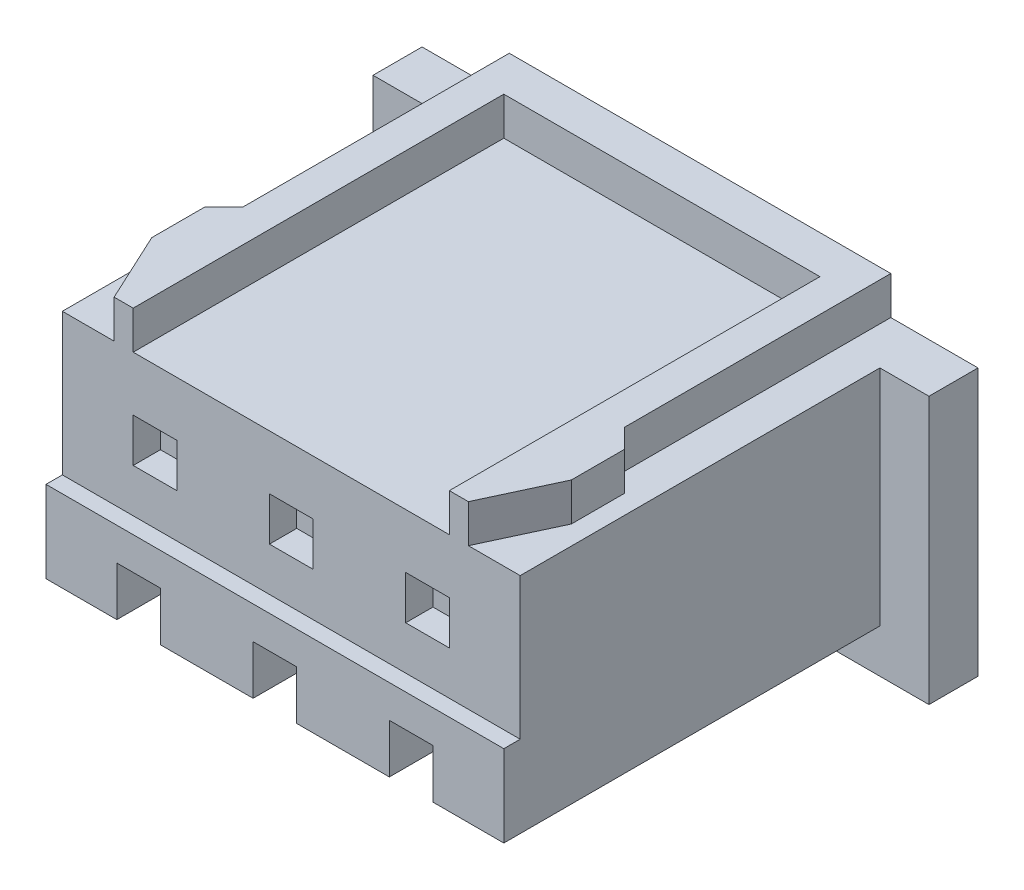
SolidWorks part; units mm, degrees
ref_plane "Plan de face" through (0, 0, 0) normal (0, 0, 1) x (1, 0, 0)
ref_plane "Plan de dessus" through (0, 0, 0) normal (0, 1, 0) x (1, 0, 0)
ref_plane "Plan de droite" through (0, 0, 0) normal (1, 0, 0) x (0, 0, -1)
sketch "Esquisse1" plane through (0, 0, 0) normal (0, 0, 1) x (1, 0, 0)
  line L1 (-5.1, 2.8) -> (5.1, 2.8)
  line L2 (-5.1, 2.8) -> (-5.1, -2.8)
  line L3 (-5.1, -2.8) -> (5.1, -2.8)
  line L4 (5.1, 2.8) -> (5.1, -2.8)
  line L5 (-5.1, 2.8) -> (5.1, -2.8) construction
  line L6 (-5.1, -2.8) -> (5.1, 2.8) construction
  point P0 (0, 0)
  dimension "D1" = 10.2
  dimension "D2" = 5.6
extrude "Boss.-Extru.1" add sketch "Esquisse1" against normal blind 7.8
sketch "Esquisse2" plane through (0, 0, 0) normal (0, 0, 1) x (1, 0, 0)
  line L0 (5.1, -2.8) -> (5.1, 2.8) construction
  line L1 (-5.1, 2.8) -> (5.1, 2.8)
  line L2 (-5.1, 2.8) -> (-5.1, -0.5)
  line L3 (-5.1, -0.5) -> (5.1, -0.5)
  line L4 (5.1, 2.8) -> (5.1, -0.5)
  dimension "D1" = 3.3
extrude "Enlèv. mat.-Extru.1" cut sketch "Esquisse2" against normal blind 0.3
sketch "Esquisse4" plane through (0, 0, 0) normal (0, 0, 1) x (1, 0, 0)
  line L0 (5.1, 2.8) -> (-5.1, 2.8) construction
  line L1 (-5.1, -2.8) -> (5.1, -2.8) construction
  line L2 (5.1, 2.8) -> (-5.1, 2.8)
  line L3 (-5.1, -2.8) -> (5.1, -2.8)
  line L4 (-4.2, 2.8) -> (-4.2, -2)
  line L5 (-4.2, -2) -> (4.2, -2)
  line L6 (4.2, -2) -> (4.2, 2.8)
  line L7 (-5.1, 2.8) -> (-5.1, -0.5) construction
  line L8 (5.1, -0.5) -> (5.1, 2.8) construction
  line L9 (-5.1, -0.5) -> (-5.1, -2.8) construction
  line L10 (5.1, -2.8) -> (5.1, -0.5) construction
  line L11 (-5.1, 2.8) -> (-5.1, -0.5)
  line L12 (-5.1, -0.5) -> (-5.1, -2.8)
  line L13 (5.1, -2.8) -> (5.1, -0.5)
  line L14 (5.1, -0.5) -> (5.1, 2.8)
  line M1 (5.1, -0.5) -> (-5.1, -0.5)
  line M2 (-5.1, -0.5) -> (-5.1, -2.8)
  line M3 (-5.1, -2.8) -> (5.1, -2.8)
  line M4 (5.1, -2.8) -> (5.1, -0.5)
  dimension "D1" = 0.9
  dimension "D2" = 0.9
  dimension "D3" = 0.8
extrude "Enlèv. mat.-Extru.2" cut sketch "Esquisse4" against normal blind 6.9 contours L2 L11 L4 M1 | L6 L5 L4 M1 M2 M3 M4 | L14 L2 L6 M1 region at (4.65, 1.15, 0) region at (0, -2.1141, 0) region at (-4.65, 1.15, 0)
sketch "Esquisse5" plane through (0, 2.8, 0) normal (0, 1, 0) x (1, 0, 0)
  line L0 (-3.5, 7.8) -> (-3.5, 2.91)
  line L1 (-3.5, 2.91) -> (-3.85, 2.56)
  line L2 (-3.85, 2.56) -> (-3.85, 1.59)
  line L3 (-3.85, 1.59) -> (-3.25, 0.3)
  line L4 (4.2, 0.3) -> (-4.2, 0.3) construction
  line L5 (-2.9, 0.3) -> (-2.9, 7.1)
  line L6 (-2.9, 7.1) -> (2.9, 7.1)
  line L7 (0, 7.8) -> (0, 0.3) construction
  line L8 (-5.1, 6.9) -> (-4.2, 6.9)
  line L9 (-4.2, 6.9) -> (-4.2, 0.3)
  line L10 (-4.2, 0.3) -> (4.2, 0.3)
  line L11 (4.2, 0.3) -> (4.2, 6.9)
  line L12 (4.2, 6.9) -> (5.1, 6.9)
  line L13 (5.1, 6.9) -> (5.1, 7.8)
  line L14 (5.1, 7.8) -> (-5.1, 7.8)
  line L15 (-5.1, 7.8) -> (-5.1, 6.9)
  line L16 (-5.1, 6.9) -> (-4.2, 6.9)
  line L17 (-4.2, 6.9) -> (-4.2, 0.3)
  line L18 (-4.2, 0.3) -> (4.2, 0.3)
  line L19 (4.2, 0.3) -> (4.2, 6.9)
  line L20 (4.2, 6.9) -> (5.1, 6.9)
  line L21 (5.1, 6.9) -> (5.1, 7.8)
  line L22 (5.1, 7.8) -> (-5.1, 7.8)
  line L23 (-5.1, 7.8) -> (-5.1, 6.9)
  line L24 (5.1, 7.8) -> (5.1, 6.9)
  line L25 (4.2, 6.9) -> (4.2, 0.3)
  line L26 (5.1, 6.9) -> (4.2, 6.9)
  line L27 (2.9, 0.3) -> (2.9, 7.1)
  line L28 (3.85, 1.59) -> (3.25, 0.3)
  line L29 (3.85, 2.56) -> (3.85, 1.59)
  line L30 (3.5, 2.91) -> (3.85, 2.56)
  line L31 (3.5, 7.8) -> (3.5, 2.91)
  point P21 (0, 7.1)
  line M9 (-5.1, 6.9) -> (-4.2, 6.9)
  line M10 (-4.2, 6.9) -> (-4.2, 0.3)
  line M11 (-4.2, 0.3) -> (4.2, 0.3)
  line M12 (4.2, 0.3) -> (4.2, 6.9)
  line M13 (4.2, 6.9) -> (5.1, 6.9)
  line M14 (5.1, 6.9) -> (5.1, 7.8)
  line M15 (5.1, 7.8) -> (-5.1, 7.8)
  line M16 (-5.1, 7.8) -> (-5.1, 6.9)
  dimension "D2" = 0.35
  dimension "D3" = 0.7
  dimension "D4" = 1.29
  dimension "D5" = 0.6
  dimension "D6" = 0.35
  dimension "D7" = 0.97
  dimension "D8" = 0.6
  dimension "D9" = 0.7
  dimension "D1" = 0
extrude "Enlèv. mat.-Extru.3" cut sketch "Esquisse5" against normal blind 0.7 contours L7 L6 L5 M11 | L6 L7 L18 L27 | L31 L30 L29 L28 M15 M11 M12 M13 M14 | L3 L2 L1 L0 M15 M16 M9 M10 M11 region at (-3.9793, 2.8, -4.6836) region at (-1.45, 2.8, -3.7) region at (1.45, 2.8, -3.7) region at (3.9793, 2.8, -4.6836)
sketch "Esquisse6" plane through (0, 0, 0) normal (0, 0, 1) x (1, 0, 0)
  line L0 (-2.9, -2) -> (-2.9, -1.1)
  line L1 (-4.2, -2) -> (4.2, -2) construction
  line L2 (-2.9, -1.1) -> (-2.1, -1.1)
  line L3 (-2.1, -1.1) -> (-2.1, -2)
  line L4 (-4.2, -0.5) -> (-4.2, -2) construction
  line L5 (-0.4, -2) -> (-0.4, -1.1)
  line L6 (-0.4, -1.1) -> (0.4, -1.1)
  line L7 (0.4, -1.1) -> (0.4, -2)
  line L9 (2.1, -2) -> (2.1, -1.1)
  line L10 (2.1, -1.1) -> (2.9, -1.1)
  line L11 (2.9, -1.1) -> (2.9, -2)
  line L13 (-2.9, -2) -> (-2.1, -2)
  line L14 (-0.4, -2) -> (0.4, -2)
  line L15 (2.1, -2) -> (2.9, -2)
  dimension "D1" = 1.3
  dimension "D2" = 0.9
  dimension "D3" = 0.8
  dimension "D4" = 1.7
  dimension "D5" = 1.7
  dimension "D6" = 0.8
  dimension "D7" = 0.8
extrude "Enlèv. mat.-Extru.4" cut sketch "Esquisse6" against normal blind 0.8
sketch "Esquisse7" plane through (0, 0, -0.3) normal (0, 0, 1) x (1, 0, 0)
  line L0 (-2.9, 2.1) -> (2.9, 2.1) construction
  line L1 (-2.9, 1.1) -> (-2.1, 1.1)
  line L2 (-2.9, 1.1) -> (-2.9, 0.3)
  line L3 (-2.9, 0.3) -> (-2.1, 0.3)
  line L4 (-2.1, 1.1) -> (-2.1, 0.3)
  line L5 (-0.4, 1.1) -> (0.4, 1.1)
  line L6 (-0.4, 1.1) -> (-0.4, 0.3)
  line L7 (-0.4, 0.3) -> (0.4, 0.3)
  line L8 (0.4, 1.1) -> (0.4, 0.3)
  line L9 (2.1, 1.1) -> (2.9, 1.1)
  line L10 (2.1, 1.1) -> (2.1, 0.3)
  line L11 (2.1, 0.3) -> (2.9, 0.3)
  line L12 (2.9, 1.1) -> (2.9, 0.3)
  line L13 (-2.9, -1.1) -> (-2.9, -2) construction
  line L14 (-0.4, -1.1) -> (-0.4, -2) construction
  line L15 (2.1, -1.1) -> (2.1, -2) construction
  dimension "D1" = 0.8
  dimension "D2" = 1
extrude "Enlèv. mat.-Extru.5" cut sketch "Esquisse7" against normal blind 0.5
sketch "Esquisse8" plane through (0, 0, -7.8) normal (0, 0, -1) x (-1, 0, 0)
  line L0 (-0.8, 1.5) -> (-0.8, -1.5)
  line L1 (-0.8, 1.5) -> (0.8, 1.5)
  line L2 (0, 1.5) -> (0, 0) construction
  line L3 (-3.5, 2.8) -> (3.5, 2.8) construction
  line L4 (-0.8, -1.5) -> (-0.4, -1.5)
  line L5 (-0.4, -1.5) -> (-0.4, -1.7)
  line L6 (-0.4, -1.7) -> (0.4, -1.7)
  line L7 (0.4, -1.7) -> (0.4, -1.5)
  line L8 (0.4, -1.5) -> (0.8, -1.5)
  line L9 (0.8, -1.5) -> (0.8, 1.5)
  line L10 (0, 0) -> (0, -1.7) construction
  line L11 (-0.7, 0.95) -> (-0.7, -1.45)
  line L12 (-0.7, -1.45) -> (0.7, -1.45)
  line L13 (0.7, -1.45) -> (0.7, 0.95)
  line L14 (0, -1.45) -> (0, 0.95) construction
  line L15 (1.7, 1.5) -> (1.7, -1.5)
  line L16 (1.7, 1.5) -> (3.3, 1.5)
  line L17 (1.7, -1.5) -> (2.1, -1.5)
  line L18 (2.1, -1.5) -> (2.1, -1.7)
  line L19 (2.1, -1.7) -> (2.9, -1.7)
  line L20 (2.9, -1.7) -> (2.9, -1.5)
  line L21 (2.9, -1.5) -> (3.3, -1.5)
  line L22 (3.3, -1.5) -> (3.3, 1.5)
  line L23 (1.8, 0.95) -> (1.8, -1.45)
  line L24 (1.8, -1.45) -> (3.2, -1.45)
  line L25 (3.2, -1.45) -> (3.2, 0.95)
  line L26 (2.5, 1.5) -> (2.5, 0) construction
  line L27 (2.5, 0) -> (2.5, -1.7) construction
  line L28 (2.5, -1.45) -> (2.5, 0.95) construction
  line L29 (-3.3, 1.5) -> (-3.3, -1.5)
  line L30 (-3.3, 1.5) -> (-1.7, 1.5)
  line L31 (-3.3, -1.5) -> (-2.9, -1.5)
  line L32 (-2.9, -1.5) -> (-2.9, -1.7)
  line L33 (-2.9, -1.7) -> (-2.1, -1.7)
  line L34 (-2.1, -1.7) -> (-2.1, -1.5)
  line L35 (-2.1, -1.5) -> (-1.7, -1.5)
  line L36 (-1.7, -1.5) -> (-1.7, 1.5)
  line L37 (-3.2, 0.95) -> (-3.2, -1.45)
  line L38 (-3.2, -1.45) -> (-1.8, -1.45)
  line L39 (-1.8, -1.45) -> (-1.8, 0.95)
  line L40 (-2.5, 1.5) -> (-2.5, 0) construction
  line L41 (-2.5, 0) -> (-2.5, -1.7) construction
  line L42 (-2.5, -1.45) -> (-2.5, 0.95) construction
  arc A0 (-0.7, 0.95) -> (0, 0.95) centre (-0.35, 0.95) cw
  arc A1 (0, 0.95) -> (0.7, 0.95) centre (0.35, 0.95) cw
  arc A2 (1.8, 0.95) -> (2.5, 0.95) centre (2.15, 0.95) cw
  arc A3 (2.5, 0.95) -> (3.2, 0.95) centre (2.85, 0.95) cw
  arc A4 (-3.2, 0.95) -> (-2.5, 0.95) centre (-2.85, 0.95) cw
  arc A5 (-2.5, 0.95) -> (-1.8, 0.95) centre (-2.15, 0.95) cw
  dimension "D1" = 3
  dimension "D2" = 1.6
  dimension "D3" = 1.3
  dimension "D4" = 0.8
  dimension "D5" = 0.2
  dimension "D6" = 0.05
  dimension "D7" = 0.1
  dimension "D8" = 0.1
  dimension "D9" = 2.4
  dimension "D11" = 2.5
  dimension "D13" = 2.5
  dimension "D10" = 2
  dimension "D12" = 2
extrude "Enlèv. mat.-Extru.6" cut sketch "Esquisse8" against normal blind 7 contours L8 L9 L1 L0 L4 L5 L6 L7 A0 A1 L13 L12 L11 | L35 L36 L30 L29 L31 L32 L33 L34 A4 A5 L39 L38 L37 | L21 L22 L16 L15 L17 L18 L19 L20 A2 A3 L25 L24 L23 region at (0, 1.4642, -7.8) region at (-2.5, 1.4642, -7.8) region at (2.5, 1.4642, -7.8)
sketch "Esquisse9" plane through (0, 0, -7.8) normal (0, 0, -1) x (-1, 0, 0)
  line L0 (-0.7, 0.95) -> (-0.7, -1.45) construction
  line L1 (-0.7, -1.45) -> (0.7, -1.45) construction
  line L2 (0.7, -1.45) -> (0.7, 0.95) construction
  line L3 (-3.2, 0.95) -> (-3.2, -1.45) construction
  line L4 (-3.2, -1.45) -> (-1.8, -1.45) construction
  line L5 (-1.8, -1.45) -> (-1.8, 0.95) construction
  line L6 (1.8, 0.95) -> (1.8, -1.45) construction
  line L7 (1.8, -1.45) -> (3.2, -1.45) construction
  line L8 (3.2, -1.45) -> (3.2, 0.95) construction
  line L9 (-0.7, 0.95) -> (-0.7, -1.45)
  line L10 (-0.7, -1.45) -> (0.7, -1.45)
  line L11 (0.7, -1.45) -> (0.7, 0.95)
  line L12 (-3.2, 0.95) -> (-3.2, -1.45)
  line L13 (-3.2, -1.45) -> (-1.8, -1.45)
  line L14 (-1.8, -1.45) -> (-1.8, 0.95)
  line L15 (1.8, 0.95) -> (1.8, -1.45)
  line L16 (1.8, -1.45) -> (3.2, -1.45)
  line L17 (3.2, -1.45) -> (3.2, 0.95)
  arc A0 (0.7, 0.95) -> (0, 0.95) centre (0.35, 0.95) ccw construction
  arc A1 (0, 0.95) -> (-0.7, 0.95) centre (-0.35, 0.95) ccw construction
  arc A2 (-1.8, 0.95) -> (-2.5, 0.95) centre (-2.15, 0.95) ccw construction
  arc A3 (-2.5, 0.95) -> (-3.2, 0.95) centre (-2.85, 0.95) ccw construction
  arc A4 (3.2, 0.95) -> (2.5, 0.95) centre (2.85, 0.95) ccw construction
  arc A5 (2.5, 0.95) -> (1.8, 0.95) centre (2.15, 0.95) ccw construction
  arc A6 (0.7, 0.95) -> (0, 0.95) centre (0.35, 0.95) ccw
  arc A7 (0, 0.95) -> (-0.7, 0.95) centre (-0.35, 0.95) ccw
  arc A8 (-1.8, 0.95) -> (-2.5, 0.95) centre (-2.15, 0.95) ccw
  arc A9 (-2.5, 0.95) -> (-3.2, 0.95) centre (-2.85, 0.95) ccw
  arc A10 (3.2, 0.95) -> (2.5, 0.95) centre (2.85, 0.95) ccw
  arc A11 (2.5, 0.95) -> (1.8, 0.95) centre (2.15, 0.95) ccw
extrude "Enlèv. mat.-Extru.7" cut sketch "Esquisse9" against normal blind 0.8
sketch "Esquisse10" plane through (0, 0, -7) normal (0, 0, -1) x (-1, 0, 0)
  line L0 (0, -1.45) -> (0, 0) construction
  line L1 (-0.7, -1.45) -> (0.7, -1.45) construction
  line L2 (-2.5, 0) -> (0, 0) construction
  line L3 (0, 0) -> (2.5, 0) construction
  line L4 (-2.5, 0) -> (-2.5, -1.45) construction
  line L5 (-3.2, -1.45) -> (-1.8, -1.45) construction
  line L6 (2.5, 0) -> (2.5, -1.45) construction
  line L7 (1.8, -1.45) -> (3.2, -1.45) construction
  circle A0 centre (0, 0) radius 0.6
  circle A1 centre (-2.5, 0) radius 0.6
  circle A2 centre (2.5, 0) radius 0.6
  dimension "D2" = 1.2
  dimension "D1" = 1.45
extrude "Enlèv. mat.-Extru.8" cut sketch "Esquisse10" against normal blind 0.5
sketch "Esquisse11" plane through (0, 0, -0.8) normal (0, 0, 1) x (1, 0, 0)
  line L0 (-2.1, -2) -> (-2.1, -1.7) construction
  line L1 (-2.1, -1.7) -> (-2.9, -1.7) construction
  line L2 (-2.9, -1.7) -> (-2.9, -2) construction
  line L3 (-2.9, -2) -> (-2.1, -2) construction
  line L4 (0.4, -2) -> (0.4, -1.7) construction
  line L5 (0.4, -1.7) -> (-0.4, -1.7) construction
  line L6 (-0.4, -1.7) -> (-0.4, -2) construction
  line L7 (-0.4, -2) -> (0.4, -2) construction
  line L8 (2.9, -1.7) -> (2.1, -1.7) construction
  line L9 (2.1, -1.7) -> (2.1, -2) construction
  line L10 (2.1, -2) -> (2.9, -2) construction
  line L11 (2.9, -2) -> (2.9, -1.7) construction
  line L12 (-2.1, -2) -> (-2.1, -1.7)
  line L13 (-2.1, -1.7) -> (-2.9, -1.7)
  line L14 (-2.9, -1.7) -> (-2.9, -2)
  line L15 (-2.9, -2) -> (-2.1, -2)
  line L16 (0.4, -2) -> (0.4, -1.7)
  line L17 (0.4, -1.7) -> (-0.4, -1.7)
  line L18 (-0.4, -1.7) -> (-0.4, -2)
  line L19 (-0.4, -2) -> (0.4, -2)
  line L20 (2.9, -1.7) -> (2.1, -1.7)
  line L21 (2.1, -1.7) -> (2.1, -2)
  line L22 (2.1, -2) -> (2.9, -2)
  line L23 (2.9, -2) -> (2.9, -1.7)
extrude "Enlèv. mat.-Extru.9" cut sketch "Esquisse11" against normal blind 2.2
